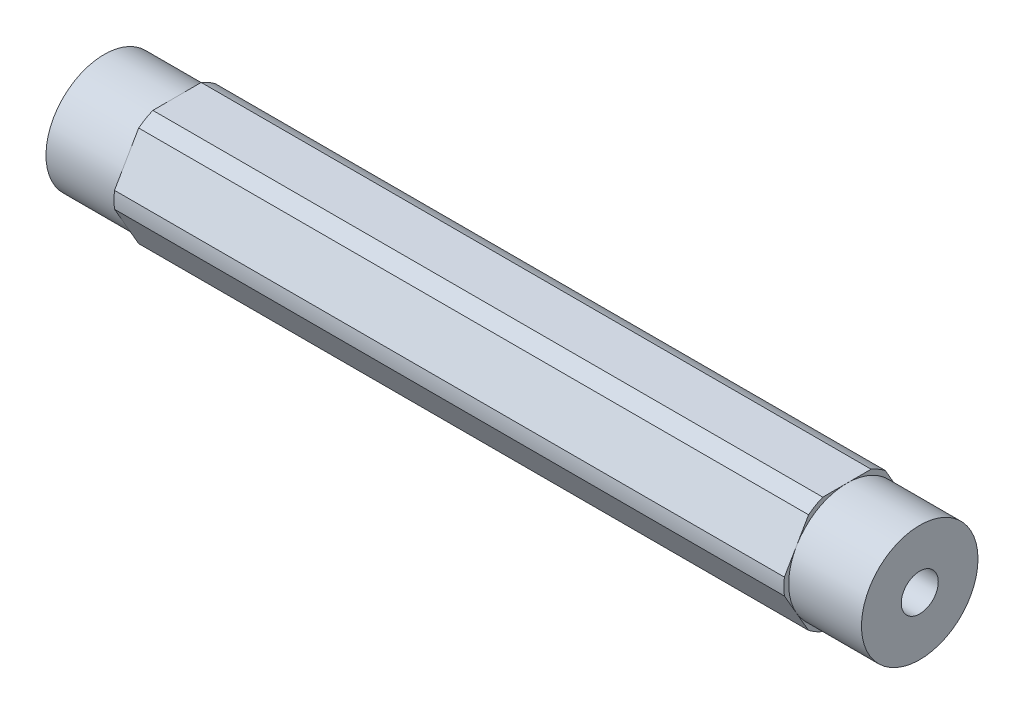
SolidWorks part; units mm, degrees
material "7075-T6 (SN)"
ref_plane "Front Plane" through (0, 0, 0) normal (0, 0, 1) x (1, 0, 0)
ref_plane "Top Plane" through (0, 0, 0) normal (0, 1, 0) x (1, 0, 0)
ref_plane "Right Plane" through (0, 0, 0) normal (1, 0, 0) x (0, 0, -1)
sketch "Sketch1" plane through (0, 0, 0) normal (1, 0, 0) x (0, 0, -1)
  line L1 (7.3323, 0) -> (3.6662, 6.35)
  line L2 (3.6662, 6.35) -> (-3.6662, 6.35)
  line L3 (-3.6662, 6.35) -> (-7.3323, 0)
  line L4 (-7.3323, 0) -> (-3.6662, -6.35)
  line L5 (-3.6662, -6.35) -> (3.6662, -6.35)
  line L6 (3.6662, -6.35) -> (7.3323, 0)
  circle A0 centre (0, 0) radius 6.875
  circle A1 centre (0, 0) radius 2.0193
  circle A2 centre (0, 0) radius 6.35 construction
  dimension "D1" = 12.7
  dimension "D2" = 13.75
  dimension "D3" = 4.0386
extrude "Boss-Extrude1" add sketch "Sketch1" along normal mid plane 88.9 contours L1 A0 L2 L3 L4 L5 L6 A1 region at (0, 0.4353, -6.6736)
sketch "Sketch2" plane through (44.45, 0, 0) normal (1, 0, 0) x (0, 0, -1)
  circle A0 centre (0, 0) radius 6.35
  dimension "D1" = 12.7
extrude "Cut-Extrude-Thin1" cut sketch "Sketch2" against normal blind 7.9375 thin thin type one direction wall 2.54
mirror "Mirror1" about plane through (0, 0, 0) normal (1, 0, 0) of "Cut-Extrude-Thin1"
equation "\"D2@Sketch1\"=13.75mm"
